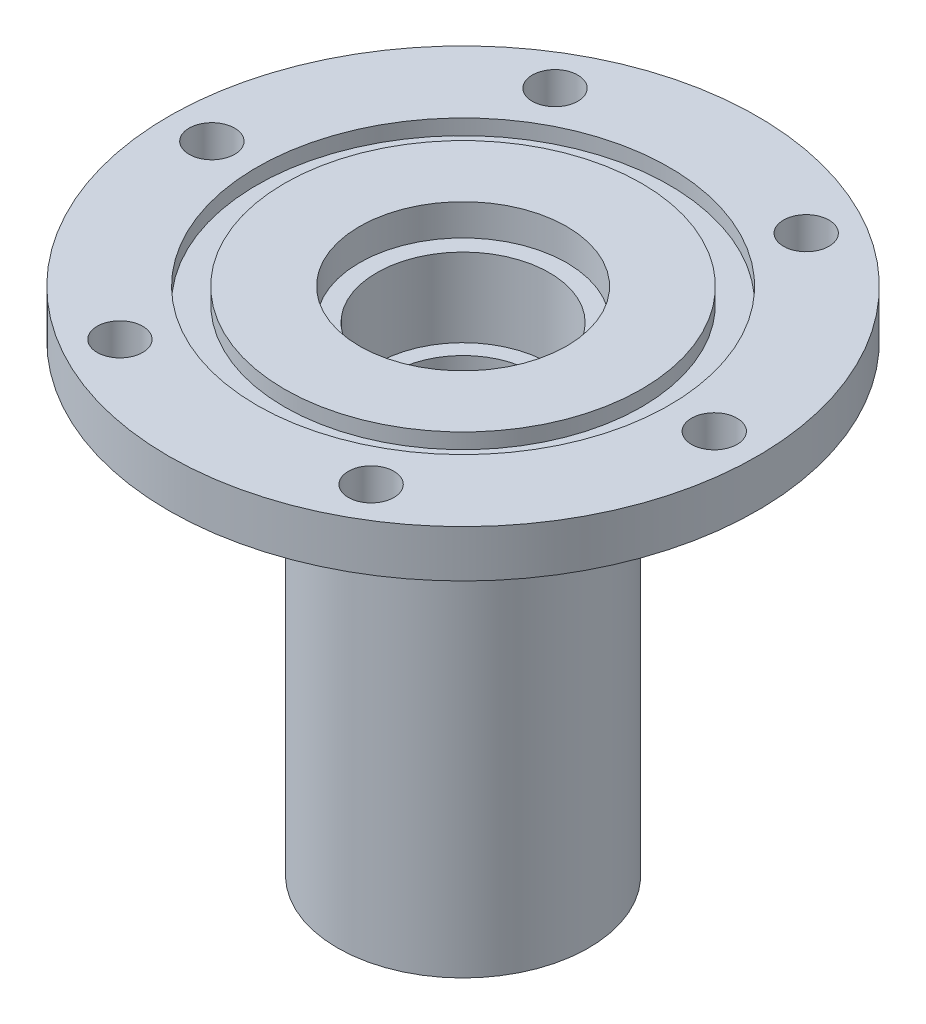
SolidWorks part; units mm, degrees
ref_plane "Front Plane" through (0, 0, 0) normal (0, 0, 1) x (1, 0, 0)
ref_plane "Top Plane" through (0, 0, 0) normal (0, 1, 0) x (1, 0, 0)
ref_plane "Right Plane" through (0, 0, 0) normal (1, 0, 0) x (0, 0, -1)
sketch "Sketch1" plane through (0, 0, 0) normal (0, 0, 1) x (1, 0, 0)
  line L0 (0, 0) -> (0, -122.9972) construction
  line L1 (37.5, 0) -> (26.2636, 0)
  line L2 (13.2, 0) -> (13.2, -4)
  line L3 (13.2, -4) -> (11, -4)
  line L4 (11, -4) -> (11, -14)
  line L9 (12.5, -65) -> (16, -65)
  line L10 (16, -65) -> (16, -6)
  line L11 (16, -6) -> (37.5, -6)
  line L12 (37.5, -6) -> (37.5, 0)
  line L23 (22.733, 0) -> (22.733, -1.9558)
  line L24 (22.733, -1.9558) -> (26.2636, -1.9558)
  line L25 (26.2636, -1.9558) -> (26.2636, 0)
  line L26 (22.733, 0) -> (13.2, 0)
  line L27 (11, -14) -> (9, -14)
  line L28 (9, -14) -> (9, -17)
  line L29 (9, -17) -> (11, -17)
  line L30 (11, -17) -> (11, -30.5)
  line L31 (12.5, -65) -> (12.5, -30.5)
  line L32 (12.5, -30.5) -> (11, -30.5)
  point P17 (0, 0)
  dimension "D1" = 22
  dimension "D2" = 26.4
  dimension "D3" = 4
  dimension "D4" = 18
  dimension "D5" = 14
  dimension "D6" = 3
  dimension "D7" = 25
  dimension "D8" = 65
  dimension "D9" = 6
  dimension "D10" = 32
  dimension "D11" = 75
  dimension "D12" = 52.5272
  dimension "D13" = 1.9558
  dimension "D14" = 3.5306
  dimension "D15" = 13.5
revolve "Revolve1" add sketch "Sketch1" angle 360 about L0
sketch "Sketch2" plane through (0, 0, 0) normal (0, 1, 0) x (1, 0, 0)
  line L1 (32, 0) -> (16, 27.7128)
  line L2 (16, 27.7128) -> (-16, 27.7128)
  line L3 (-16, 27.7128) -> (-32, 0)
  line L4 (-32, 0) -> (-16, -27.7128)
  line L5 (-16, -27.7128) -> (16, -27.7128)
  line L6 (16, -27.7128) -> (32, 0)
  circle A0 centre (0, 0) radius 32 construction
  circle A1 centre (32, 0) radius 2.75
  circle A2 centre (32, 0) radius 5
  dimension "D1" = 64
  dimension "D2" = 10
  dimension "D3" = 5.5
hole_wizard "M5 Clearance Hole1" positions "Sketch3" profile "Sketch4" hole size "M5" standard "ANSI Metric" end condition through all
sketch "Sketch3" plane through (0, 0, 0) normal (0, 1, 0) x (1, 0, 0)
  point P0 (16, 27.7128)
  point P3 (32, 0)
  point P6 (16, -27.7128)
  point P9 (-16, -27.7128)
  point P12 (-32, 0)
  point P15 (-16, 27.7128)
sketch "Sketch4" plane through (16, 0, -27.7128) normal (1, 0, 0) x (0, 0, 1)
  line L0 (0, 0) -> (0, 65)
  line L1 (0, 65) -> (2.9, 65)
  line L2 (2.9, 65) -> (2.9, 0)
  line L5 (2.9, 0) -> (0, 0)
  line L11 (0, -6.35) -> (0, 107.95) construction
  dimension "Thru Hole Dia." = 5.8
  dimension "Thru Hole Depth" = 65
fillet "Fillet1" radius 5 1 edges at (0, -6, 16)
